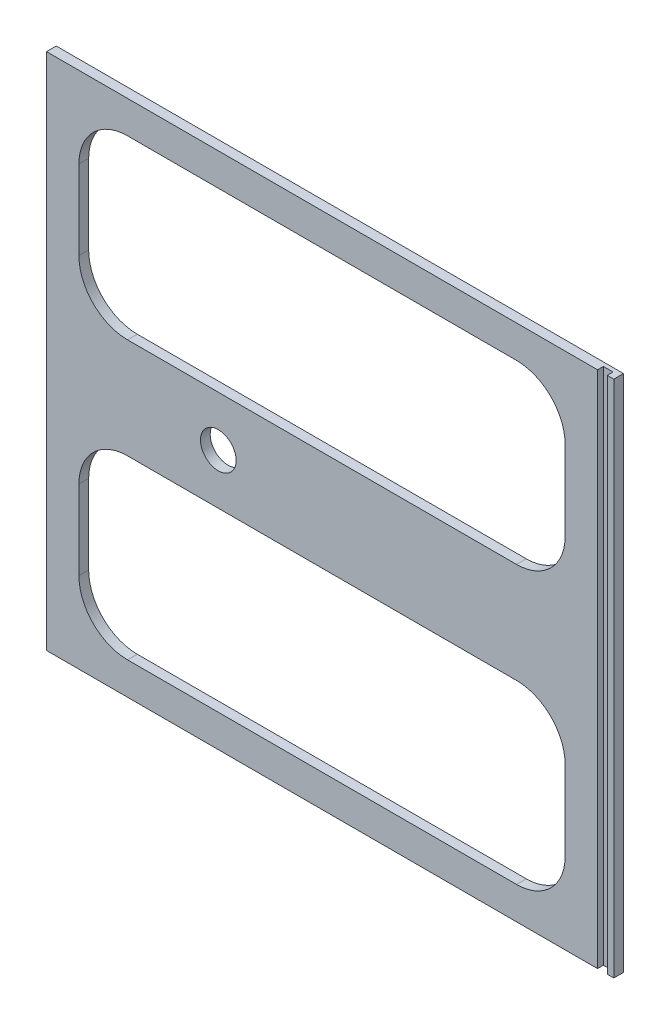
SolidWorks part; units mm, degrees
ref_plane "Front Plane" through (0, 0, 0) normal (0, 0, 1) x (1, 0, 0)
ref_plane "Top Plane" through (0, 0, 0) normal (0, 1, 0) x (1, 0, 0)
ref_plane "Right Plane" through (0, 0, 0) normal (1, 0, 0) x (0, 0, -1)
sketch "Sketch1" plane through (0, 0, 0) normal (0, 0, 1) x (1, 0, 0)
  line L1 (0, 0) -> (87.5, 0)
  line L2 (0, 0) -> (0, 80)
  line L3 (0, 80) -> (87.5, 80)
  line L4 (87.5, 0) -> (87.5, 80)
  dimension "D1" = 80
  dimension "D2" = 87.5
extrude "Boss-Extrude1" add sketch "Sketch1" along normal blind 1.5
sketch "Sketch2" plane through (0, 80, 0) normal (0, 1, 0) x (1, 0, 0)
  line L1 (87.5, -1.5) -> (0, -1.5) construction
  line L2 (86.5, -0.6) -> (85, -0.6)
  line L5 (85, -0.6) -> (85, -1.5)
  line L21 (85, -1.5) -> (86.5, -1.5)
  line L27 (86.5, -0.6) -> (87.5, -0.6) construction
  line L28 (87.5, -1.5) -> (87.5, 0) construction
  line L29 (86.5, -0.6) -> (86.5, -1.5)
  line M7 (0, -1.5) -> (87.5, -1.5)
  dimension "D1" = 1
  dimension "D2" = 1.5
  dimension "D3" = 0.9
extrude "Cut-Extrude1" cut sketch "Sketch2" against normal up to surface (80 mm away) contours L29 M7 region at (85.75, 80, 1.05) up to face at (43.75, 0, 0.75)
sketch "Sketch3" plane through (0, 0, 0) normal (0, 0, -1) x (-1, 0, 0)
  circle A1 centre (-26.5, 40) radius 2.75
  dimension "D1" = 5.5
extrude "Cut-Extrude2" cut sketch "Sketch3" against normal up to surface (1.5 mm away) up to face at (42.5, 40, 1.5)
sketch "Sketch4" plane through (0, 0, 1.5) normal (0, 0, 1) x (1, 0, 0)
  line L0 (5, 75) -> (0, 75) construction
  line L1 (12.5, 75) -> (72.5, 75)
  line L2 (5, 67.5) -> (5, 55.25)
  line L3 (12.5, 47.75) -> (72.5, 47.75)
  line L4 (80, 67.5) -> (80, 55.25)
  line L5 (0, 80) -> (0, 0) construction
  line L6 (0, 75) -> (5, 75)
  line L7 (5, 75) -> (5, 80) construction
  line L8 (85, 80) -> (0, 80) construction
  line L9 (80, 75) -> (85, 75)
  line L10 (85, 0) -> (85, 80) construction
  line L11 (26.5, 42.75) -> (26.5, 47.75) construction
  line L12 (23.75, 40) -> (0, 40) construction
  line L13 (12.5, 32.25) -> (72.5, 32.25)
  line L14 (80, 12.5) -> (80, 24.75)
  line L15 (12.5, 5) -> (72.5, 5)
  line L16 (5, 12.5) -> (5, 24.75)
  circle A0 centre (26.5, 40) radius 2.75 construction
  arc A1 (5, 55.25) -> (12.5, 47.75) centre (12.5, 55.25) ccw
  arc A2 (72.5, 47.75) -> (80, 55.25) centre (72.5, 55.25) ccw
  arc A3 (72.5, 75) -> (80, 67.5) centre (72.5, 67.5) cw
  arc A4 (12.5, 75) -> (5, 67.5) centre (12.5, 67.5) ccw
  arc A5 (12.5, 5) -> (5, 12.5) centre (12.5, 12.5) cw
  arc A6 (80, 12.5) -> (72.5, 5) centre (72.5, 12.5) cw
  arc A7 (72.5, 32.25) -> (80, 24.75) centre (72.5, 24.75) cw
  arc A8 (12.5, 32.25) -> (5, 24.75) centre (12.5, 24.75) ccw
  point P26 (5, 47.75)
  point P29 (80, 47.75)
  point P38 (5, 5)
  point P41 (80, 5)
  point P44 (80, 32.25)
  point P47 (5, 32.25)
  dimension "D5" = 7.5
  dimension "D6" = 7.5
  dimension "D1" = 5
  dimension "D2" = 5
  dimension "D3" = 5
  dimension "D4" = 5
extrude "Cut-Extrude3" cut sketch "Sketch4" against normal up to surface (1.5 mm away) contours L4 L1 L2 L3 | L16 L15 L14 L13 region at (42.5, 61.375, 1.5) region at (42.5, 18.625, 1.5) up to face at (23.75, 40, 0)
